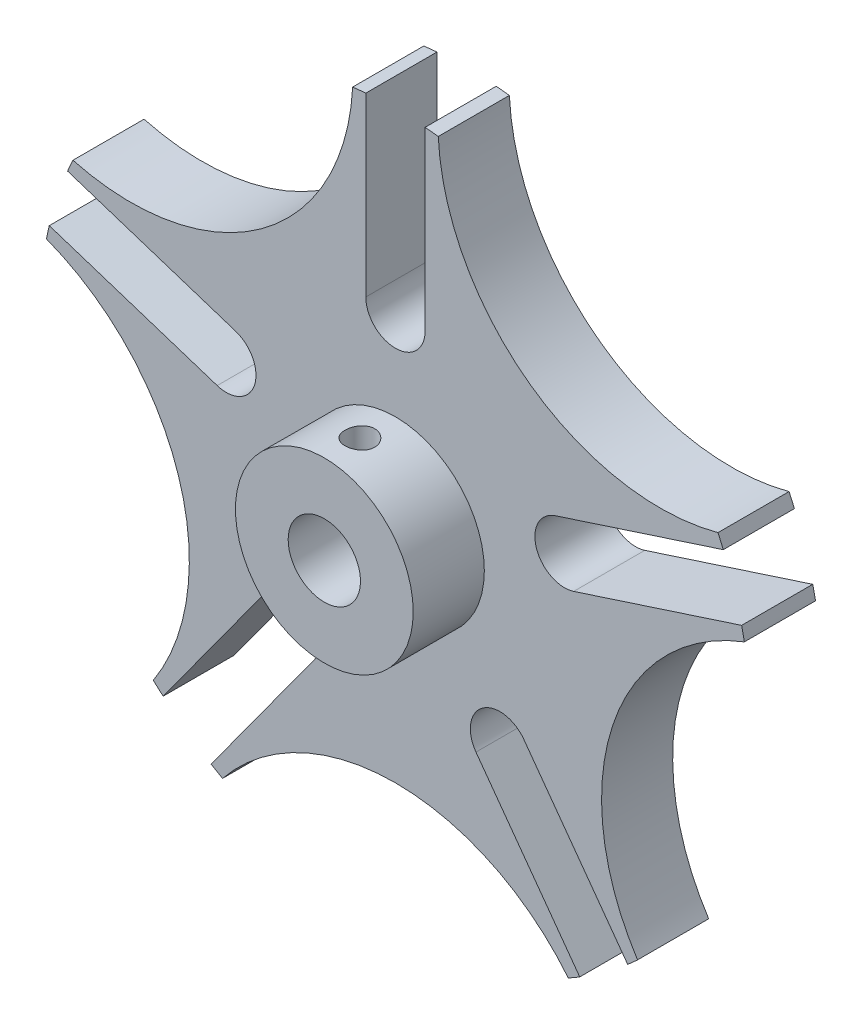
SolidWorks part; units mm, degrees
ref_plane "Front Plane" through (0, 0, 0) normal (0, 0, 1) x (1, 0, 0)
ref_plane "Top Plane" through (0, 0, 0) normal (0, 1, 0) x (1, 0, 0)
ref_plane "Right Plane" through (0, 0, 0) normal (1, 0, 0) x (0, 0, -1)
ref_axis "Axis1" through (0, 0, -9.6) along (0, 0, 1)
sketch "Sketch1" plane through (0, 0, 0) normal (0, 0, 1) x (1, 0, 0)
  circle A1 centre (0, 0) radius 7.5
  dimension "D1" = 15
extrude "Extrude1" add sketch "Sketch1" against normal mid plane 6
sketch "Sketch2" plane through (0, 0, -3) normal (0, 0, -1) x (-1, 0, 0)
  circle A0 centre (0, 0) radius 30 construction
  circle A1 centre (0, 0) radius 30
extrude "Extrude2" add sketch "Sketch2" along normal blind 6
sketch "Sketch3" plane through (0, 0, -9) normal (0, 0, -1) x (-1, 0, 0)
  line L0 (0, -38) -> (0, 9.4316) construction
  circle A1 centre (0, -38) radius 18.5
  circle A2 centre (0, 0) radius 30 construction
  dimension "D1" = 38
  dimension "D2" = 37
extrude "Cut-Extrude1" cut sketch "Sketch3" against normal through all
sketch "Sketch4" plane through (0, 0, -9) normal (0, 0, -1) x (-1, 0, 0)
  line L0 (0, 0) -> (25.4577, -35.0395) construction
  line L1 (0, 0) -> (25.4577, -35.0395) construction
  line L2 (6.7942, -13.6047) -> (15.5497, -25.6556)
  line L3 (10.8393, -10.6658) -> (19.5948, -22.7166)
  line L5 (2.0225, 1.4695) -> (27.4802, -33.57) construction
  line L6 (-2.0225, -1.4695) -> (23.4351, -36.509) construction
  circle A0 centre (0, 0) radius 15 construction
  arc A1 (10.8393, -10.6658) -> (6.7942, -13.6047) centre (8.8168, -12.1353) ccw
  circle A2 centre (0, -15.2858) radius 2.5 construction
  arc A3 (15.5497, -25.6556) -> (19.5948, -22.7166) centre (0, 0) ccw
  circle A4 centre (0, 0) radius 30 construction
  point P8 (8.8168, -12.1353)
  dimension "D1" = 30
extrude "Cut-Extrude2" cut sketch "Sketch4" against normal through all
sketch "Sketch8" plane through (0, 0, -9) normal (0, 0, -1) x (-1, 0, 0)
  circle A0 centre (0, -38) radius 18.75
  arc A2 (14.362, -26.3388) -> (-14.362, -26.3388) centre (0, -38) ccw construction
  dimension "D1" = 0.25
extrude "Extrude3" cut sketch "Sketch8" against normal through all
pattern_circular "CirPattern1" count 5 over 360 about axis through (0, 0, -9.6) along (0, 0, 1) of "Cut-Extrude1", "Cut-Extrude2", "Extrude3"
sketch "Sketch5" plane through (0, 0, -9) normal (0, 0, -1) x (-1, 0, 0)
  circle A1 centre (0, 0) radius 3.05
  dimension "D1" = 6.1
extrude "Cut-Extrude3" cut sketch "Sketch5" against normal through all
ref_plane "Plane1" through (0, 7.5, 0) normal (0, 1, 0) x (-1, 0, 0)
hole_wizard "M3x0.5 Tapped Hole1" positions "Sketch7" profile "Sketch6" tap size "M3x0.5" standard "Ansi Metric"
sketch "Sketch7" plane through (0, 7.5, 0) normal (0, 1, 0) x (-1, 0, 0)
  point P0 (0, 0)
sketch "Sketch6" plane through (0, 7.5, 0) normal (1, 0, 0) x (0, 0, 1)
  line L0 (0, 0) -> (0, 8.2511)
  line L1 (0, 8.2511) -> (1.25, 7.5)
  line L2 (1.25, 7.5) -> (1.25, 0)
  line L5 (1.25, 0) -> (0, 0)
  line L10 (0, 8.2511) -> (-1.25, 7.5) construction
  line L11 (0, -6.35) -> (0, 107.95) construction
  dimension "Tap Drill Dia." = 2.5
  dimension "Tap Drill Depth" = 7.5
  dimension "Drill Angle" = 118
cosmetic thread "Hole Thread1" parameters "D1"=5.3349, "D2"=3
sketch "Sketch9" plane through (0, 0, -9) normal (0, 0, -1) x (-1, 0, 0)
  line L0 (0, 0) -> (0, -49.052) construction
